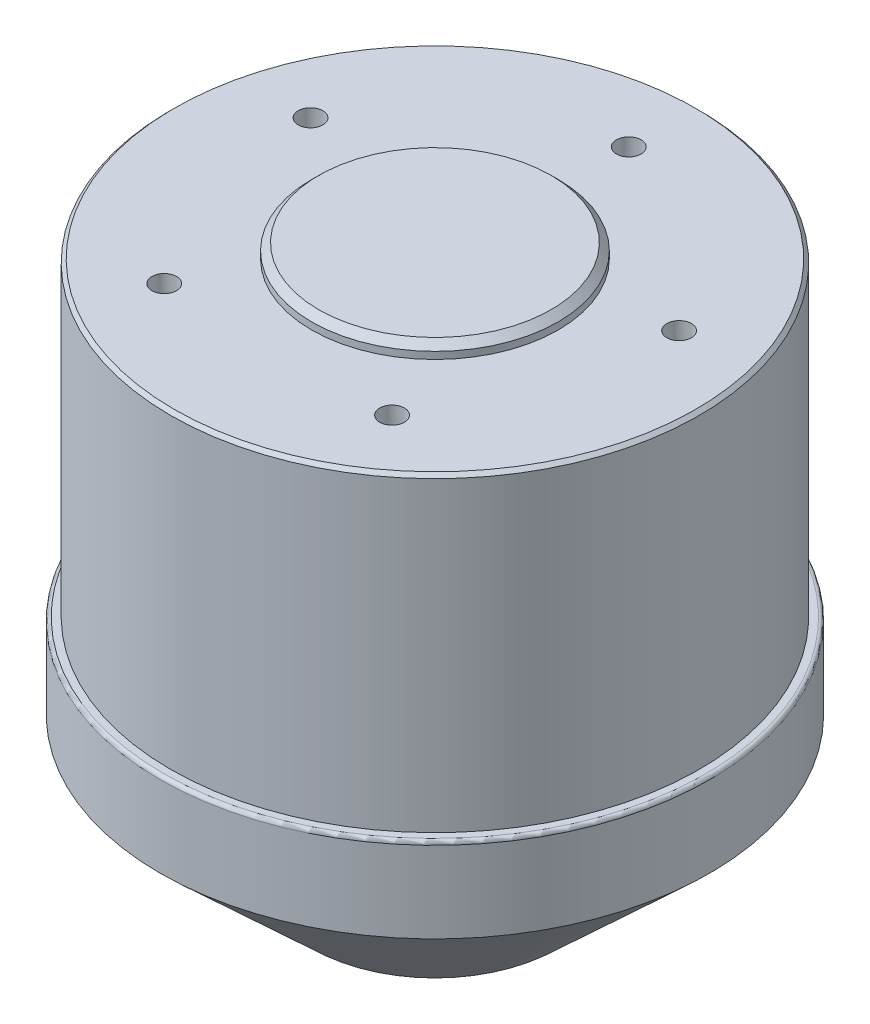
SolidWorks part; units mm, degrees
ref_plane "Front Plane" through (0, 0, 0) normal (0, 0, 1) x (1, 0, 0)
ref_plane "Top Plane" through (0, 0, 0) normal (0, 1, 0) x (1, 0, 0)
ref_plane "Right Plane" through (0, 0, 0) normal (1, 0, 0) x (0, 0, -1)
sketch "Sketch1" plane through (0, 0, 0) normal (0, 1, 0) x (1, 0, 0)
  circle A0 centre (0, 0) radius 39
  circle A1 centre (0, 0) radius 37.5
  circle A2 centre (0, 0) radius 17.5
  dimension "D1" = 78
  dimension "D2" = 75
  dimension "D3" = 35
extrude "Boss-Extrude1" add sketch "Sketch1" along normal blind 76 contours A1 A2 region at (-36.4393, 0, 0)
extrude "Boss-Extrude2" add sketch "Sketch1<3>" along normal blind 78 contours A2 region at (0, 0, 0)
sketch "Sketch1<3>" plane through (0, 0, 0) normal (0, 1, 0) x (1, 0, 0) same geometry as "Sketch1"
extrude "Boss-Extrude3" add sketch "Sketch1<4>" along normal blind 32 contours A0 A1 region at (-37.8969, 0, 0)
sketch "Sketch1<4>" plane through (0, 0, 0) normal (0, 1, 0) x (1, 0, 0) same geometry as "Sketch1"
sketch "Sketch2" plane through (0, 76, 0) normal (0, 1, 0) x (1, 0, 0)
  circle A0 centre (0, 0) radius 27.5
  circle A1 centre (0, 27.5) radius 1.75
  circle A2 centre (26.1541, 8.498) radius 1.75
  circle A3 centre (16.1641, -22.248) radius 1.75
  circle A4 centre (-16.1641, -22.248) radius 1.75
  circle A5 centre (-26.1541, 8.498) radius 1.75
  point P15 (0, 0)
  dimension "D1" = 55
  dimension "D3" = 3.5
  dimension "D2" = 5
extrude "Cut-Extrude1" cut sketch "Sketch2" against normal blind 7 contours A1 | A2 | A3 | A4 | A5
fillet "Fillet1" radius 0.5 1 edges at (0, 32, 39)
chamfer "Chamfer1" distance 0.5 1 edges at (0, 76, 37.5)
chamfer "Chamfer2" distance 21.5 distance2 20 1 edges at (0, 0, 39) first distance on face at (0, 0, 39)
chamfer "Chamfer3" distance 1 1 edges at (0, 78, 17.5)
sketch "Sketch4" plane through (0, 0, 0) normal (0, -1, 0) x (1, 0, 0)
  circle A0 centre (0, 0) radius 4
  dimension "D1" = 8
extrude "Cut-Extrude2" cut sketch "Sketch4" against normal offset from surface (68 mm away) 10 up to face at (0, 78, 16.5)
